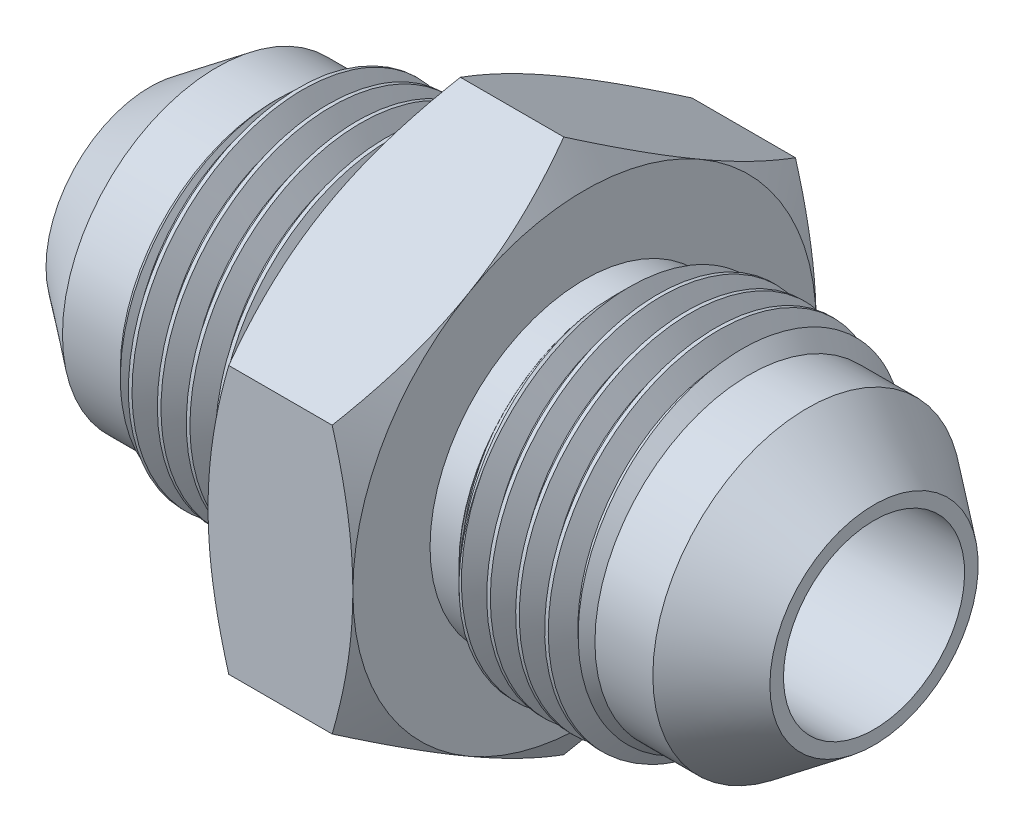
SolidWorks part; units mm, degrees
note: '?' marks a value the reader was unsure of.
ref_plane "Front" through (0, 0, 0) normal (0, 0, 1) x (1, 0, 0)
ref_plane "Top" through (0, 0, 0) normal (0, 1, 0) x (1, 0, 0)
ref_plane "Right" through (0, 0, 0) normal (1, 0, 0) x (0, 0, -1)
sketch "Sketch6" plane through (0, 0, 0) normal (0, 0, 1) x (1, 0, 0)
  line L1 (19.8438, 9.525) -> (19.8438, -9.525) construction
  line L2 (-19.8438, 0) -> (19.8438, 0)
  line L4 (-19.8438, 0) -> (-19.8438, 9.525)
  line L5 (-19.8438, 9.525) -> (19.8438, 9.525)
  line L6 (19.8438, 0) -> (19.8438, 9.525)
  point P4 (3.9688, 0)
  point P6 (-3.9688, 0)
  dimension "D1" = 15.875
  dimension "Straight Dia" = 19.05
  dimension "Length" = 39.6875
  dimension "L1" = 15.875
revolve "Revolve3" add sketch "Sketch6" angle 360 about L2
sketch "Sketch14" plane through (-19.8438, 0, 0) normal (-1, 0, 0) x (0, 0, 1)
  circle A1 centre (0, 0) radius 9.525
  circle A2 centre (0, 0) radius 9.525
  dimension "D1" = 0
curve "Helix/Spiral1" pitch 1.5875 height 17.4625 turns 11 parameters "Pitch"=1.5875
sketch "Sketch15" plane through (0, 0, 0) normal (0, 0, 1) x (1, 0, 0)
  line L0 (-21.2328, 9.525) -> (-19.8438, 9.525)
  line L1 (-19.8438, 9.525) -> (-20.4391, 8.4939)
  line L2 (-20.4391, 8.4939) -> (-20.6375, 8.4939)
  line L3 (-20.6375, 8.4939) -> (-21.2328, 9.525)
  line L4 (-20.5383, 8.4939) -> (-20.5383, 9.525) construction
  line L5 (-20.9352, 9.0094) -> (-20.1414, 9.0094) construction
  dimension "D1" = 60
  dimension "D2" = 0.1984
  dimension "D3" = 0.7937
sweep "Cut-Sweep1" cut profiles "Sketch15" path "Helix/Spiral1" align with end faces yes
sketch "Sketch16" plane through (0, 0, 0) normal (1, 0, 0) x (0, 0, -1)
  line L0 (-9.525, 0) -> (9.525, 0) construction
  circle A0 centre (0, 0) radius 9.525 construction
ref_axis "Axis1" through (0, 0, 9.525) along (0, 0, -1)?
pattern_circular "CirPattern1" count 2 every 180 about axis through (0, 0, 9.525) along (0, 0, -1) of "Cut-Sweep1"
ref_plane "Plane1" through (-3.9688, 0, 0) normal (1, 0, 0) x (0, 0, -1)
sketch "Sketch12" plane through (-3.9688, 0, 0) normal (1, 0, 0) x (0, 0, -1)
  line L1 (0, 14.6647) -> (-12.7, 7.3323)
  line L2 (-12.7, 7.3323) -> (-12.7, -7.3323)
  line L3 (-12.7, -7.3323) -> (0, -14.6647)
  line L4 (0, -14.6647) -> (12.7, -7.3323)
  line L5 (12.7, -7.3323) -> (12.7, 7.3323)
  line L6 (12.7, 7.3323) -> (0, 14.6647)
  circle A0 centre (0, 0) radius 12.7 construction
  dimension "Hex" = 25.4
extrude "Extrude1" add sketch "Sketch12" along normal up to vertex (7.9375 mm away) up to point (3.9688, 0, 0)
sketch "Sketch7" plane through (0, 0, 0) normal (0, 0, 1) x (1, 0, 0)
  line L0 (-19.8438, 0) -> (-19.8438, 4.9657)
  line L2 (-19.8438, 4.9657) -> (19.8438, 4.9657)
  line L4 (19.8438, 0) -> (19.8438, 9.525) construction
  line L11 (19.8438, 4.9657) -> (19.8438, 0)
  line L12 (19.8438, 0) -> (-19.8438, 0)
  line L13 (-19.8438, 4.9657) -> (-19.8438, -4.9657) construction
  dimension "ID" = 9.9314
sketch "Sketch10" plane through (0, 0, 0) normal (0, 0, 1) x (1, 0, 0)
  line L0 (-19.8438, 9.525) -> (19.8438, 9.525) construction
  line L1 (-11.0245, -9.525) -> (-11.0245, 9.525) construction
  line L2 (-19.8438, 0) -> (-19.8438, 9.525) construction
  line L3 (-6.6128, 9.525) -> (-5.5563, 8.4685)
  line L4 (-21.2328, 9.525) -> (-19.8438, 9.525) construction
  line L5 (0, 0) -> (-19.8438, 0) construction
  line L6 (6.6128, 9.525) -> (3.9688, 9.525)
  line L8 (-5.5563, 8.4685) -> (-3.9688, 8.4685)
  line L9 (3.9688, 8.4685) -> (3.9688, 9.525)
  line L11 (0, 0) -> (0, 14.6647) construction
  line L12 (3.9688, 14.6647) -> (-3.9688, 14.6647) construction
  line L13 (-19.8438, 5.7106) -> (-19.8438, 9.525)
  line L14 (-16.1838, 8.4685) -> (-19.8438, 5.7106)
  line L15 (-13.0088, 8.4685) -> (-16.1838, 8.4685)
  line L16 (-11.9523, 9.525) -> (-13.0088, 8.4685)
  line L17 (-19.8438, 9.525) -> (-11.9523, 9.525)
  line L18 (-3.9688, 8.4685) -> (-3.9688, 9.525)
  line L19 (-6.6128, 9.525) -> (-3.9688, 9.525)
  line L20 (-3.9688, -12.7) -> (-3.9688, 12.7) construction
  line L21 (19.8438, 9.525) -> (11.9523, 9.525)
  line L22 (11.9523, 9.525) -> (13.0088, 8.4685)
  line L23 (13.0088, 8.4685) -> (16.1838, 8.4685)
  line L24 (16.1838, 8.4685) -> (19.8438, 5.7106)
  line L25 (19.8438, 5.7106) -> (19.8438, 9.525)
  line L26 (5.5563, 8.4685) -> (3.9688, 8.4685)
  line L27 (6.6128, 9.525) -> (5.5563, 8.4685)
  point P9 (-11.0245, -9.525)
  point P24 (-11.0245, 0)
  dimension "D1" = 11.4211
  dimension "D2" = 0.0254
  dimension "D3" = 3.175
  dimension "D4" = 37
  dimension "D5" = 1.5875
  dimension "D6" = 45
  dimension "D7" = 45
  dimension "D8" = 1.9844
revolve "Cut-Revolve6" cut sketch "Sketch10" angle 360 about L2
revolve "Cut-Revolve5" cut sketch "Sketch7" angle 360 about L12
sketch "Sketch13" plane through (0, 0, 0) normal (0, 0, 1) x (1, 0, 0)
  line L0 (-3.9688, 14.6647) -> (-3.9688, 12.7)
  line L1 (-3.9688, 7.3323) -> (-3.9688, 14.6647) construction
  line L2 (-3.9688, 12.7) -> (-2.8344, 14.6647)
  line L3 (-2.8344, 14.6647) -> (-3.9688, 14.6647)
  line L4 (2.8344, 14.6647) -> (3.9688, 12.7)
  line L5 (3.9688, 14.6647) -> (3.9688, 7.3323) construction
  line L6 (3.9688, 12.7) -> (3.9688, 14.6647)
  line L7 (3.9688, 14.6647) -> (2.8344, 14.6647)
  dimension "D2" = 30
revolve "Cut-Revolve7" cut sketch "Sketch13" angle 360 about L2
equation "\"D3@Helix/Spiral1\" = \"L1@Sketch6\"+\"Pitch@Helix/Spiral1\""
equation "\"D2@Sketch15\" = \"Pitch@Helix/Spiral1\"*.125"
equation "\"D3@Sketch15\" = \"Pitch@Helix/Spiral1\"*.5"
equation "\"D3@Sketch10\" = \"Pitch@Helix/Spiral1\"*2"
equation "\"D5@Sketch10\" = \"Pitch@Helix/Spiral1\""
equation "\"D1@Sketch10\" = \"ID@Sketch7\"*1.15"
equation "\"D1@Sketch6\" = \"L1@Sketch6\""
equation "\"D8@Sketch10\" = \"Pitch@Helix/Spiral1\"*1.25"
